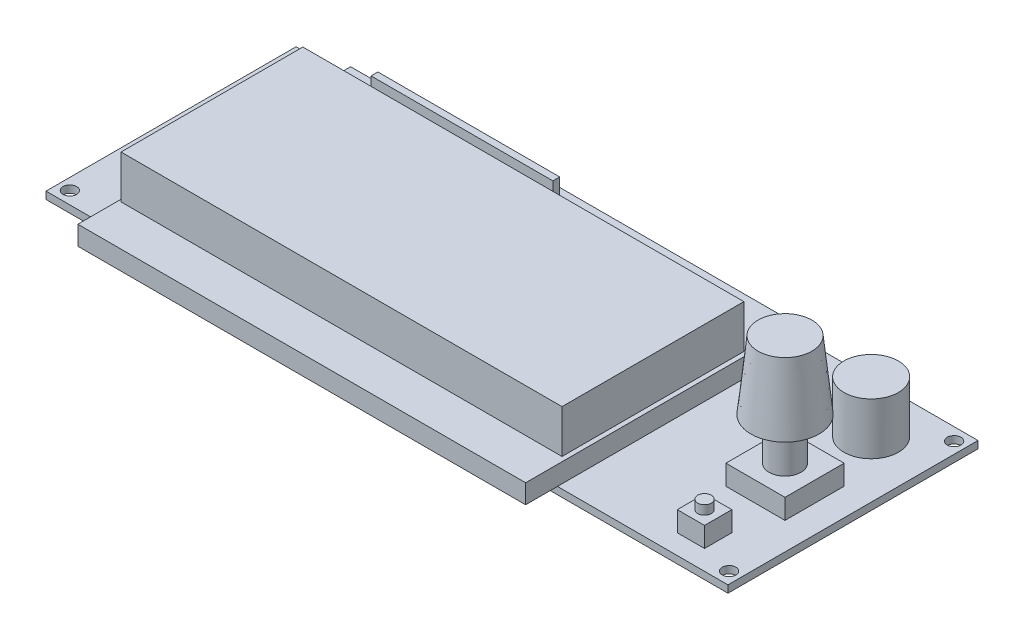
SolidWorks part; units mm, degrees
ref_plane "Front Plane" through (0, 0, 0) normal (0, 0, 1) x (1, 0, 0)
ref_plane "Top Plane" through (0, 0, 0) normal (0, 1, 0) x (1, 0, 0)
ref_plane "Right Plane" through (0, 0, 0) normal (1, 0, 0) x (0, 0, -1)
sketch "Sketch1" plane through (0, 0, 0) normal (0, 1, 0) x (1, 0, 0)
  line L1 (-75, -27.5) -> (75, -27.5)
  line L2 (-75, -27.5) -> (-75, 27.5)
  line L3 (-75, 27.5) -> (75, 27.5)
  line L4 (75, -27.5) -> (75, 27.5)
  line L5 (-75, -27.5) -> (75, 27.5) construction
  line L6 (-75, 27.5) -> (75, -27.5) construction
  point P0 (0, 0)
  dimension "D1" = 150
  dimension "D2" = 55
extrude "MainPCB" add sketch "Sketch1" along normal blind 1.6
sketch "Sketch2" plane through (0, 1.6, 0) normal (0, 1, 0) x (1, 0, 0)
  line L0 (0, 27.5) -> (0, -27.5) construction
  line L1 (75, 27.5) -> (-75, 27.5) construction
  line L2 (-75, -27.5) -> (75, -27.5) construction
  line L3 (75, 0) -> (-75, 0) construction
  line L4 (-75, 27.5) -> (-75, -27.5) construction
  line L5 (-72.5, -24.75) -> (-72.5, 24.75) construction
  line L6 (72.5, -24.75) -> (72.5, 24.75) construction
  circle A0 centre (-72.5, 24.75) radius 1.5
  circle A1 centre (-72.5, -24.75) radius 1.5
  circle A2 centre (72.5, -24.75) radius 1.5
  circle A3 centre (72.5, 24.75) radius 1.5
  point P15 (-72.5, 0)
  point P17 (0, 0)
  point P21 (72.5, 0)
  dimension "D1" = 3
  dimension "D2" = 24.75
  dimension "D3" = 72.5
extrude "ScrewHoles" cut sketch "Sketch2" against normal through all
sketch "Sketch3" plane through (0, 1.6, 0) normal (0, 1, 0) x (1, 0, 0)
  line L0 (75, 27.5) -> (-75, 27.5) construction
  line L1 (-61, 25.5) -> (37.5, 25.5)
  line L2 (-61, 25.5) -> (-61, -34.5)
  line L3 (-61, -34.5) -> (37.5, -34.5)
  line L4 (37.5, 25.5) -> (37.5, -34.5)
  line L5 (-61, 25.5) -> (37.5, -34.5) construction
  line L6 (-61, -34.5) -> (37.5, 25.5) construction
  line L7 (-75, 27.5) -> (-75, -27.5) construction
  dimension "D1" = 98.5
  dimension "D2" = 60
  dimension "D3" = 2
  dimension "D4" = 14
extrude "Boss-Extrude2" add sketch "Sketch3" along normal blind 4.2
sketch "Sketch4" plane through (0, 5.8, 0) normal (0, 1, 0) x (1, 0, 0)
  line L0 (37.5, -27.5) -> (75, -27.5) construction
  line L1 (-60.5, 14.5) -> (36.5, 14.5)
  line L2 (-60.5, 14.5) -> (-60.5, -25.5)
  line L3 (-60.5, -25.5) -> (36.5, -25.5)
  line L4 (36.5, 14.5) -> (36.5, -25.5)
  line L5 (-60.5, 14.5) -> (36.5, -25.5) construction
  line L6 (-60.5, -25.5) -> (36.5, 14.5) construction
  line L7 (-75, 27.5) -> (-75, -27.5) construction
  point P0 (-12, -5.5)
  point P8 (-75, 0)
  dimension "D1" = 97
  dimension "D2" = 40
  dimension "D3" = 2
  dimension "D4" = 14.5
extrude "Boss-Extrude3" add sketch "Sketch4" along normal blind 9.5
sketch "Sketch5" plane through (0, 1.6, 0) normal (0, 1, 0) x (1, 0, 0)
  line L0 (62.5, 27.5) -> (62.5, -27.5) construction
  line L1 (75, 27.5) -> (-75, 27.5) construction
  line L3 (37.5, -27.5) -> (75, -27.5) construction
  line L5 (56, 4.05) -> (69, 4.05)
  line L6 (56, 4.05) -> (56, -8.95)
  line L7 (56, -8.95) -> (69, -8.95)
  line L8 (69, 4.05) -> (69, -8.95)
  line L9 (56, 4.05) -> (69, -8.95) construction
  line L10 (56, -8.95) -> (69, 4.05) construction
  line L11 (59.5, -17.15) -> (65.5, -17.15)
  line L12 (59.5, -17.15) -> (59.5, -23.15)
  line L13 (59.5, -23.15) -> (65.5, -23.15)
  line L14 (65.5, -17.15) -> (65.5, -23.15)
  line L15 (59.5, -17.15) -> (65.5, -23.15) construction
  line L16 (59.5, -23.15) -> (65.5, -17.15) construction
  circle A0 centre (72.5, -24.75) radius 1.5 construction
  circle A1 centre (62.5, 16.5) radius 6
  point P8 (62.5, -20.15)
  point P11 (62.5, -2.45)
  dimension "D1" = 10
  dimension "D2" = 12
  dimension "D3" = 11
  dimension "D4" = 6
  dimension "D5" = 6
  dimension "D6" = 1.6
  dimension "D7" = 13
  dimension "D8" = 13
  dimension "D9" = 22.3
extrude "Boss-Extrude4" add sketch "Sketch5" along normal blind 4.4
sketch "Sketch6" plane through (0, 6, 0) normal (0, 1, 0) x (1, 0, 0)
  line L0 (62.5, -17.15) -> (62.5, -23.15) construction
  line L1 (65.5, -17.15) -> (59.5, -17.15) construction
  line L2 (59.5, -23.15) -> (65.5, -23.15) construction
  circle A0 centre (62.5, -20.15) radius 1.5
  dimension "D1" = 3
extrude "Boss-Extrude5" add sketch "Sketch6" along normal blind 2
sketch "Sketch7" plane through (0, 6, 0) normal (0, 1, 0) x (1, 0, 0)
  circle A0 centre (62.5, 16.5) radius 6
  circle A1 centre (62.5, 16.5) radius 6 construction
extrude "Boss-Extrude6" add sketch "Sketch7" along normal blind 7
sketch "Sketch8" plane through (0, 6, 0) normal (0, 1, 0) x (1, 0, 0)
  line L0 (62.5, 4.05) -> (62.5, -8.95) construction
  line L1 (69, 4.05) -> (56, 4.05) construction
  line L2 (56, -8.95) -> (69, -8.95) construction
  circle A0 centre (62.5, -2.45) radius 3.5
  dimension "D1" = 7
extrude "Boss-Extrude7" add sketch "Sketch8" along normal up to surface (9.3 mm away) up to face at (-12, 15.3, 5.5)
sketch "Sketch9" plane through (0, 15.3, 0) normal (0, 1, 0) x (1, 0, 0)
  circle A0 centre (62.5, -2.45) radius 7.5
  circle A3 centre (62.5, -2.45) radius 3.5 construction
  dimension "D1" = 15
extrude "Boss-Extrude8" add sketch "Sketch9" along normal blind 15 draft 6
sketch "Sketch10" plane through (0, 5.8, 0) normal (0, 1, 0) x (1, 0, 0)
  line L0 (-75, 27.5) -> (-75, -27.5) construction
  line L1 (-52, 22.5) -> (-12, 22.5)
  line L2 (-52, 22.5) -> (-52, 21)
  line L3 (-52, 21) -> (-12, 21)
  line L4 (-12, 22.5) -> (-12, 21)
  line L5 (-52, 22.5) -> (-12, 21) construction
  line L6 (-52, 21) -> (-12, 22.5) construction
  line L8 (75, 27.5) -> (-75, 27.5) construction
  point P0 (-32, 21.75)
  dimension "D1" = 1.5
  dimension "D2" = 40
  dimension "D3" = 23
  dimension "D4" = 6.5
extrude "AnnoyinglyPlacedPins" add sketch "Sketch10" along normal blind 5
